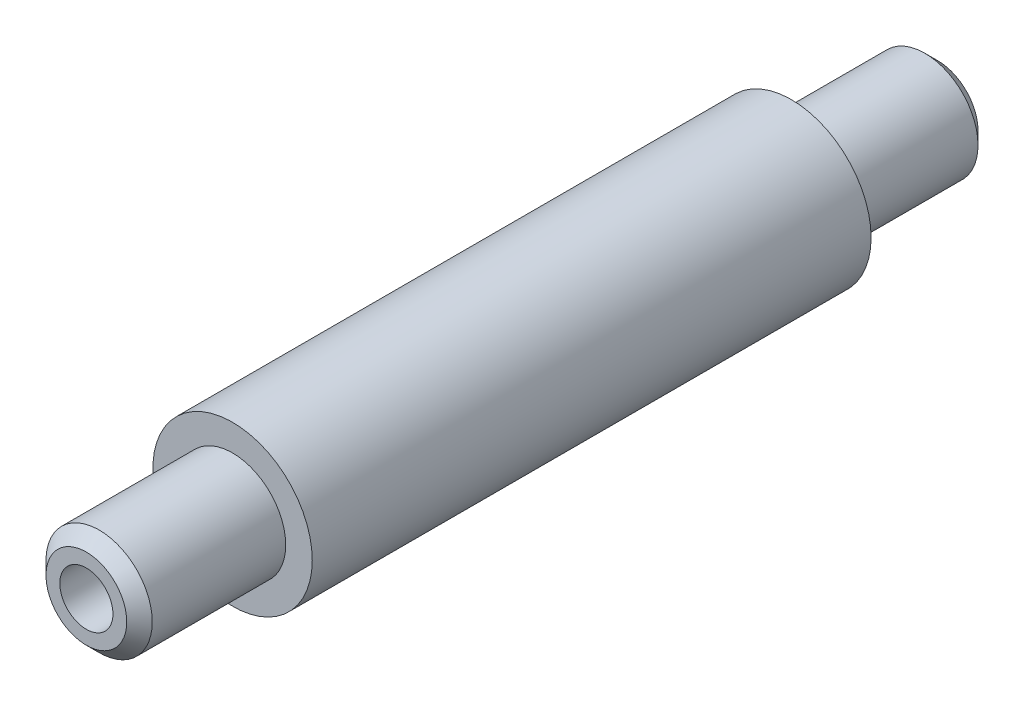
SolidWorks part; units mm, degrees
material "AISI 1020 Steel, Cold Rolled"
ref_plane "Front Plane" through (0, 0, 0) normal (0, 0, 1) x (1, 0, 0)
ref_plane "Top Plane" through (0, 0, 0) normal (0, 1, 0) x (1, 0, 0)
ref_plane "Right Plane" through (0, 0, 0) normal (1, 0, 0) x (0, 0, -1)
ref_axis "X-axis" through (-88.99, 0, 0) along (1, 0, 0)
ref_axis "Y-axis" through (0, 55, 0) along (0, -1, 0)
ref_axis "Z-axis" through (0, 0, -88.99) along (0, 0, 1)
sketch "Sketch1" plane through (0, 0, 0) normal (1, 0, 0) x (0, 0, -1)
  line L0 (0, 0) -> (101.6, 0) construction
  line L1 (-0.1524, 3.175) -> (101.6, 3.175)
  line L2 (101.6, 3.175) -> (101.6, 4.826)
  line L3 (100.076, 6.35) -> (84.1248, 6.35)
  line L4 (84.1248, 6.35) -> (84.1248, 9.525)
  line L5 (84.1248, 9.525) -> (17.3228, 9.525)
  line L6 (17.3228, 9.525) -> (17.3228, 6.35)
  line L7 (17.3228, 6.35) -> (1.3716, 6.35)
  line L8 (-0.1524, 4.826) -> (-0.1524, 3.175)
  line L9 (101.6, 4.826) -> (100.076, 6.35)
  line L10 (1.3716, 6.35) -> (-0.1524, 4.826)
  point P5 (0, 3.175)
  point P6 (101.6, 6.35)
  point P11 (-0.1524, 6.35)
  point P12 (0, 0)
  point P13 (0, 0)
  point P14 (0, 0)
  point P15 (0, 0)
  point P16 (0, 0)
  dimension "D1" = 101.6
  dimension "D2" = 6.35
  dimension "D3" = 12.7
  dimension "D4" = 19.05
  dimension "D5" = 12.7
  dimension "D6" = 17.4752
  dimension "D7" = 66.802
revolve "Revolve1" add sketch "Sketch1" angle 360 about L0
